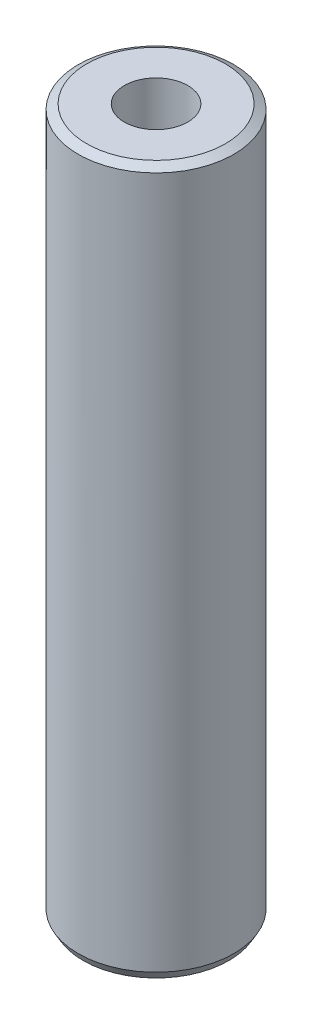
SolidWorks part; units mm, degrees
ref_plane "Front Plane" through (0, 0, 0) normal (0, 0, 1) x (1, 0, 0)
ref_plane "Top Plane" through (0, 0, 0) normal (0, 1, 0) x (1, 0, 0)
ref_plane "Right Plane" through (0, 0, 0) normal (1, 0, 0) x (0, 0, -1)
sketch "Sketch1" plane through (0, 0, 0) normal (0, 1, 0) x (1, 0, 0)
  circle A0 centre (0, 0) radius 30
  dimension "SHAFT_OD" = 60
extrude "Boss-Extrude1" add sketch "Sketch1" along normal blind 272.1016
sketch "Sketch2" plane through (0, 0, 0) normal (0, 1, 0) x (1, 0, 0)
  circle A0 centre (0, 0) radius 12.2341
  dimension "BORE_D" = 24.4681
extrude "Cut-Extrude1" cut sketch "Sketch2" along normal through all
chamfer "Chamfer1" distance 1.8899 angle 60 2 edges at (0, 272.1016, 30) (0, 0, 30) first distance on face at (0, 272.1016, 30) first distance on face at (0, 0, 12.2341)
